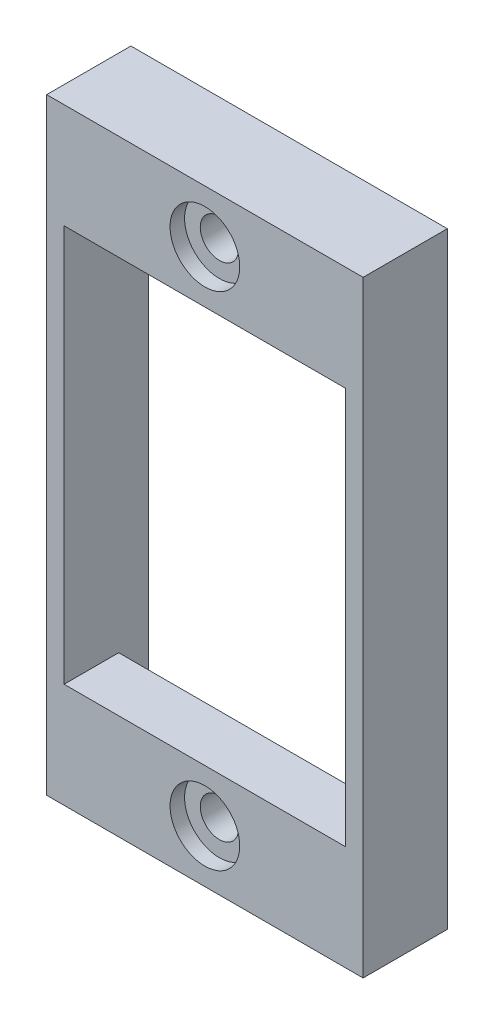
SolidWorks part; units mm, degrees
ref_plane "Front" through (0, 0, 0) normal (0, 0, 1) x (1, 0, 0)
ref_plane "Top" through (0, 0, 0) normal (0, 1, 0) x (1, 0, 0)
ref_plane "Right" through (0, 0, 0) normal (1, 0, 0) x (0, 0, -1)
sketch "Sketch1" plane through (0, 0, 0) normal (0, 0, 1) x (1, 0, 0)
  line L0 (0, 24.5) -> (0, -24.5) construction
  line L1 (-12, -24.5) -> (12, -24.5) construction
  line L2 (-12, -24.5) -> (-12, 24.5) construction
  line L3 (-12, 24.5) -> (12, 24.5) construction
  line L4 (12, -24.5) -> (12, 24.5) construction
  line L5 (-12, 0) -> (12, 0) construction
  line L6 (-12.12, -24.62) -> (-12.12, 24.62)
  line L7 (-12.12, 24.62) -> (12.12, 24.62)
  line L8 (12.12, -24.62) -> (12.12, 24.62)
  line L9 (-12.12, -24.62) -> (12.12, -24.62)
  line L10 (-13.62, -26.12) -> (-13.62, 26.12)
  line L11 (-13.62, 26.12) -> (13.62, 26.12)
  line L12 (13.62, -26.12) -> (13.62, 26.12)
  line L13 (-13.62, -26.12) -> (13.62, -26.12)
  circle A0 centre (0, 21.59) radius 1.5 construction
  circle A1 centre (0, -21.59) radius 1.5 construction
  dimension "D3" = 3
  dimension "D4" = 2.91
  dimension "D1" = 49
  dimension "D2" = 24
  dimension "D5" = 43.18
  dimension "D6" = 0.12
  dimension "D7" = 1.5
extrude "Boss-Extrude1" add sketch "Sketch1" along normal blind 0.25 and the other way blind 1.7
sketch "Sketch2" plane through (0, 0, 0.25) normal (0, 0, 1) x (1, 0, 0)
  line L0 (-12.12, 17.09) -> (12.12, 17.09)
  line L1 (-12.12, 24.62) -> (-12.12, -24.62) construction
  line L2 (12.12, -24.62) -> (12.12, 24.62) construction
  line L4 (13.62, -26.12) -> (13.62, 26.12) construction
  line L5 (13.62, -26.12) -> (13.62, 26.12)
  line L6 (-13.62, 26.12) -> (13.62, 26.12) construction
  line L7 (-13.62, 26.12) -> (13.62, 26.12)
  line L8 (-13.62, -26.12) -> (-13.62, 26.12) construction
  line L9 (-13.62, -26.12) -> (-13.62, 26.12)
  line L10 (-13.62, -26.12) -> (13.62, -26.12) construction
  line L11 (-13.62, -26.12) -> (13.62, -26.12)
  line L12 (-12, 0) -> (12, 0) construction
  line L13 (-12, 0) -> (12, 0) construction
  line L14 (-12.12, -17.09) -> (12.12, -17.09)
  line L15 (-12.12, 17.09) -> (-12.12, -17.09)
  line L16 (12.12, 17.09) -> (12.12, -17.09)
  circle A0 centre (0, 21.59) radius 1.5 construction
  dimension "D1" = 3
extrude "Boss-Extrude2" add sketch "Sketch2" along normal blind 1
sketch "Sketch3" plane through (0, 0, 1.25) normal (0, 0, 1) x (1, 0, 0)
  line L0 (12.12, 17.09) -> (-12.12, 17.09) construction
  line L1 (-4.62, 17.09) -> (-7.62, 17.09)
  line L2 (-12.12, -17.09) -> (12.12, -17.09) construction
  line L3 (-7.62, -17.09) -> (-4.62, -17.09)
  line L4 (-7.62, 17.09) -> (-7.62, -17.09)
  line L5 (-13.62, -26.12) -> (-13.62, 26.12) construction
  line L6 (-4.62, 17.09) -> (-4.62, -17.09)
  dimension "D1" = 6
  dimension "D2" = 3
extrude "Boss-Extrude3" add sketch "Sketch3" against normal up to surface (1 mm away) up to face at (0, 20.855, 0.25)
sketch "Sketch4" plane through (0, 0, 1.25) normal (0, 0, 1) x (1, 0, 0)
  line L0 (-13.62, 26.12) -> (-13.62, -26.12) construction
  line L1 (-7.62, -17.09) -> (-13.62, -17.09)
  line L2 (-7.62, -17.09) -> (-7.62, 17.09)
  line L3 (-7.62, 17.09) -> (-13.62, 17.09)
  line L4 (-13.62, -17.09) -> (-13.62, 17.09)
  line L5 (-7.62, 17.09) -> (-12.12, 17.09) construction
extrude "Cut-Extrude1" cut sketch "Sketch4" against normal up to surface (2.95 mm away) up to face at (0, 0, -1.7)
sketch "Sketch5" plane through (0, 24.62, 0) normal (0, -1, 0) x (1, 0, 0)
  line L0 (0, 0.25) -> (0, -1.7) construction
  line L1 (12.12, 0.25) -> (-12.12, 0.25) construction
  line L2 (12.12, -1.7) -> (-12.12, -1.7) construction
  line L4 (1.5, -1.5) -> (-1.5, -1.5)
  line L5 (1.5, -1.5) -> (1.5, -1.7)
  line L6 (1.5, -1.7) -> (-1.5, -1.7)
  line L7 (-1.5, -1.5) -> (-1.5, -1.7)
  line L8 (1.5, -1.5) -> (-1.5, -1.7) construction
  line L9 (1.5, -1.7) -> (-1.5, -1.5) construction
  point P6 (0, -1.6)
  dimension "D1" = 1.75
  dimension "D2" = 3
extrude "Boss-Extrude4" add sketch "Sketch5" along normal blind 0.5
mirror "Mirror1" about plane through (0, 0, 0) normal (0, 1, 0) of "Boss-Extrude4"
sketch "Sketch6" plane through (0, 0, -1.7) normal (0, 0, -1) x (-1, 0, 0)
  line L20 (13.62, -26.12) -> (13.62, -17.09)
  line L21 (13.62, -17.09) -> (12.12, -17.09)
  line L22 (12.12, -17.09) -> (12.12, -24.62)
  line L23 (12.12, -24.62) -> (1.5, -24.62)
  line L24 (1.5, -24.62) -> (1.5, -24.12)
  line L25 (1.5, -24.12) -> (-1.5, -24.12)
  line L26 (-1.5, -24.12) -> (-1.5, -24.62)
  line L27 (-1.5, -24.62) -> (-12.12, -24.62)
  line L28 (-12.12, -24.62) -> (-12.12, 24.62)
  line L29 (-12.12, 24.62) -> (-1.5, 24.62)
  line L30 (-1.5, 24.62) -> (-1.5, 24.12)
  line L31 (-1.5, 24.12) -> (1.5, 24.12)
  line L32 (1.5, 24.12) -> (1.5, 24.62)
  line L33 (1.5, 24.62) -> (12.12, 24.62)
  line L34 (12.12, 24.62) -> (12.12, 17.09)
  line L35 (12.12, 17.09) -> (13.62, 17.09)
  line L36 (13.62, 17.09) -> (13.62, 26.12)
  line L37 (13.62, 26.12) -> (-13.62, 26.12)
  line L38 (-13.62, 26.12) -> (-13.62, -26.12)
  line L39 (-13.62, -26.12) -> (13.62, -26.12)
  line L40 (13.62, -26.12) -> (13.62, -17.09)
  line L41 (13.62, -17.09) -> (12.12, -17.09)
  line L42 (12.12, -17.09) -> (12.12, -24.62)
  line L43 (12.12, -24.62) -> (1.5, -24.62)
  line L44 (1.5, -24.62) -> (1.5, -24.12)
  line L45 (1.5, -24.12) -> (-1.5, -24.12)
  line L46 (-1.5, -24.12) -> (-1.5, -24.62)
  line L47 (-1.5, -24.62) -> (-12.12, -24.62)
  line L48 (-12.12, -24.62) -> (-12.12, 24.62)
  line L49 (-12.12, 24.62) -> (-1.5, 24.62)
  line L50 (-1.5, 24.62) -> (-1.5, 24.12)
  line L51 (-1.5, 24.12) -> (1.5, 24.12)
  line L52 (1.5, 24.12) -> (1.5, 24.62)
  line L53 (1.5, 24.62) -> (12.12, 24.62)
  line L54 (12.12, 24.62) -> (12.12, 17.09)
  line L55 (12.12, 17.09) -> (13.62, 17.09)
  line L56 (13.62, 17.09) -> (13.62, 26.12)
  line L57 (13.62, 26.12) -> (-13.62, 26.12)
  line L58 (-13.62, 26.12) -> (-13.62, -26.12)
  line L59 (-13.62, -26.12) -> (13.62, -26.12)
  dimension "D1" = 0
extrude "Boss-Extrude5" add sketch "Sketch6" along normal blind 0.6
fillet "Fillet1" radius 1 4 edges at (1.5, -24.62, -1.9) (-1.5, -24.62, -1.9) (1.5, 24.62, -1.9) (-1.5, 24.62, -1.9)
sketch "Sketch8" plane through (0, 0, 1.25) normal (0, 0, 1) x (1, 0, 0)
  line L0 (-4.62, -17.09) -> (-4.62, 17.09) construction
  line L1 (-4.62, -17.09) -> (-4.62, 17.09)
  line L2 (12.12, 17.09) -> (-4.62, 17.09) construction
  line L3 (12.12, 17.09) -> (-4.62, 17.09)
  line L4 (-4.62, -17.09) -> (12.12, -17.09) construction
  line L5 (-4.62, -17.09) -> (12.12, -17.09)
  line L6 (12.12, -17.09) -> (12.12, 17.09) construction
  line L7 (12.12, -17.09) -> (12.12, 17.09)
  line L8 (-7.62, -17.09) -> (-13.62, -17.09)
  line L9 (-13.62, -17.09) -> (-13.62, -26.12)
  line L10 (-13.62, -26.12) -> (13.62, -26.12)
  line L11 (13.62, -26.12) -> (13.62, 26.12)
  line L12 (13.62, 26.12) -> (-13.62, 26.12)
  line L13 (-13.62, 26.12) -> (-13.62, 17.09)
  line L14 (-13.62, 17.09) -> (-7.62, 17.09)
  line L15 (-7.62, 17.09) -> (-7.62, -17.09)
  line L16 (-7.62, -17.09) -> (-13.62, -17.09)
  line L17 (-13.62, -17.09) -> (-13.62, -26.12)
  line L18 (-13.62, -26.12) -> (13.62, -26.12)
  line L19 (13.62, -26.12) -> (13.62, 26.12)
  line L20 (13.62, 26.12) -> (-13.62, 26.12)
  line L21 (-13.62, 26.12) -> (-13.62, 17.09)
  line L22 (-13.62, 17.09) -> (-7.62, 17.09)
  line L23 (-7.62, 17.09) -> (-7.62, -17.09)
  dimension "D1" = 0
extrude "Boss-Extrude6" add sketch "Sketch8" along normal blind 3.7
sketch "Sketch7" plane through (0, 0, 0.25) normal (0, 0, -1) x (-1, 0, 0)
  circle A2 centre (0, 21.59) radius 1.65
  circle A3 centre (0, -21.59) radius 1.65
  dimension "D1" = 3.3
extrude "Cut-Extrude2" cut sketch "Sketch7" against normal up to surface (4.7 mm away) up to face at (-5.31, 0, 4.95)
sketch "Sketch10" plane through (0, 0, 4.95) normal (0, 0, 1) x (1, 0, 0)
  line L0 (13.62, 0) -> (-7.62, 0) construction
  line L1 (13.62, -26.12) -> (13.62, 26.12) construction
  line L2 (-7.62, 17.09) -> (-7.62, -17.09) construction
  circle A0 centre (0, 21.59) radius 3
  circle A1 centre (0, -21.59) radius 3
  dimension "D1" = 6
extrude "Cut-Extrude3" cut sketch "Sketch10" against normal blind 1.25
sketch "Sketch11" plane through (0, 0, 0.25) normal (0, 0, -1) x (-1, 0, 0)
  line L0 (4.62, 0) -> (-12.12, 0) construction
  line L1 (4.62, 17.09) -> (4.62, -17.09) construction
  line L2 (-12.12, -24.62) -> (-12.12, -17.09) construction
  line L8 (-12.12, 0.995) -> (8.88, 0.995) construction
  line L9 (-12.12, 0.995) -> (-12.12, 16.095) construction
  line L10 (-12.12, 16.095) -> (8.88, 16.095) construction
  line L11 (8.88, 0.995) -> (8.88, 16.095) construction
  line L12 (8.88, 8.545) -> (-12.12, 8.545) construction
  line L13 (-12.12, -17.09) -> (-12.12, 17.09) construction
  line L14 (-1.62, 0.995) -> (-1.62, 16.095) construction
  line L15 (-4.87, 5.895) -> (1.63, 5.895) construction
  line L16 (-4.87, 5.895) -> (-4.87, 12.395) construction
  line L17 (-4.87, 12.395) -> (1.63, 12.395) construction
  line L18 (1.63, 5.895) -> (1.63, 12.395) construction
  line L19 (-4.87, 5.895) -> (1.63, 12.395) construction
  line L20 (-4.87, 12.395) -> (1.63, 5.895) construction
  line L21 (-4.87, -12.395) -> (1.63, -5.895) construction
  line L22 (-4.87, -5.895) -> (1.63, -12.395) construction
  line L23 (1.63, -5.895) -> (1.63, -12.395) construction
  line L24 (-4.87, -12.395) -> (1.63, -12.395) construction
  line L25 (-4.87, -5.895) -> (-4.87, -12.395) construction
  line L26 (-4.87, -5.895) -> (1.63, -5.895) construction
  line L27 (-1.62, -0.995) -> (-1.62, -16.095) construction
  line L28 (8.88, -8.545) -> (-12.12, -8.545) construction
  line L29 (8.88, -0.995) -> (8.88, -16.095) construction
  line L30 (-12.12, -16.095) -> (8.88, -16.095) construction
  line L31 (-12.12, -0.995) -> (-12.12, -16.095) construction
  line L32 (-12.12, -0.995) -> (8.88, -0.995) construction
  line L33 (-0.12, -1.995) -> (-0.12, -0.995) construction
  line L34 (-3.12, 1.995) -> (-0.12, 1.995) construction
  line L35 (-3.12, 1.995) -> (-3.12, 0.995) construction
  line L36 (-3.12, 0.995) -> (-0.12, 0.995) construction
  line L37 (-0.12, 1.995) -> (-0.12, 0.995) construction
  line L38 (-3.12, 1.995) -> (-0.12, 0.995) construction
  line L39 (-3.12, 0.995) -> (-0.12, 1.995) construction
  line L40 (-3.12, -0.995) -> (-0.12, -1.995) construction
  line L41 (-3.12, -1.995) -> (-0.12, -0.995) construction
  line L42 (-3.12, -1.995) -> (-0.12, -1.995) construction
  line L43 (-3.12, -1.995) -> (-3.12, -0.995) construction
  line L44 (4.62, 0) -> (4.62, 17.09) construction
  circle A0 centre (-1.62, 9.145) radius 1.5 construction
  circle A2 centre (-9.21, 8.545) radius 1.5 construction
  circle A3 centre (5.97, 8.545) radius 1.5 construction
  circle A4 centre (5.97, -8.545) radius 1.5 construction
  circle A5 centre (-9.21, -8.545) radius 1.5 construction
  circle A6 centre (-1.62, -9.145) radius 1.5 construction
  point P8 (-1.62, 8.545)
  point P13 (4.62, 8.545)
  point P15 (-1.62, 9.145)
  point P49 (-1.62, -9.145)
  point P50 (-1.62, -8.545)
  point P51 (-1.62, 1.495)
  dimension "D5" = 3
  dimension "D6" = 3
  dimension "D7" = 1.41
  dimension "D8" = 1
  dimension "D1" = 21
  dimension "D2" = 15.1
  dimension "D3" = 6.5
  dimension "D4" = 0.6
  dimension "D9" = 3
sketch "Sketch12" plane through (0, 0, 0.25) normal (0, 0, -1) x (-1, 0, 0)
  line L0 (-4.87, 5.895) -> (-4.87, 12.395) construction
  line L1 (-12.12, -17.09) -> (-5.87, -17.09)
  line L2 (-12.12, -17.09) -> (-12.12, 17.09)
  line L3 (-12.12, 17.09) -> (-5.87, 17.09)
  line L4 (-5.87, -17.09) -> (-5.87, 17.09)
  line L6 (7.62, 17.09) -> (12.12, 17.09) construction
  line L7 (2.63, -17.09) -> (9.87, -17.09)
  line L8 (2.63, -17.09) -> (2.63, 17.09)
  line L9 (2.63, 17.09) -> (9.87, 17.09)
  line L10 (9.87, -17.09) -> (9.87, 17.09)
  line L11 (1.63, 5.895) -> (1.63, 12.395) construction
  line L13 (-12.12, 17.09) -> (4.62, 17.09) construction
  line L14 (4.62, -17.09) -> (-12.12, -17.09) construction
  dimension "D1" = 1
  dimension "D2" = 1
extrude "Boss-Extrude7" add sketch "Sketch12" against normal up to surface (4.7 mm away) up to face at (3, 21.59, 4.95)
sketch "Sketch18" plane through (0, 0, 0.25) normal (0, 0, -1) x (-1, 0, 0)
  line L0 (2.63, -17.09) -> (9.87, -17.09)
  line L1 (9.87, -17.09) -> (9.87, 17.09)
  line L2 (9.87, 17.09) -> (2.63, 17.09)
  line L3 (2.63, 17.09) -> (2.63, -17.09)
extrude "Cut-Extrude6" cut sketch "Sketch18" against normal up to surface (4.7 mm away) up to face at (-5.8725, 0, 4.95)
sketch "Sketch19" plane through (0, -17.09, 0) normal (0, 1, 0) x (1, 0, 0)
  line L0 (-13.62, 2.3) -> (-13.62, -4.95) construction
  line L1 (-13.62, 2.3) -> (-13.62, -4.95)
  line L2 (-13.62, 2.3) -> (-12.12, 2.3) construction
  line L3 (-13.62, 2.3) -> (-12.12, 2.3)
  line L4 (-12.12, 2.3) -> (-12.12, -4.95)
  line L5 (-13.62, -4.95) -> (5.87, -4.95) construction
  line L6 (-12.12, -4.95) -> (-13.62, -4.95)
extrude "Boss-Extrude8" add sketch "Sketch19" along normal up to surface (34.18 mm away) up to face at (-6.6233, 17.09, 0.9667)
sketch "Sketch20" plane through (0, 0, 0.25) normal (0, 0, -1) x (-1, 0, 0)
  line L0 (-5.87, -17.09) -> (-5.87, 17.09) construction
  line L1 (-5.87, -17.09) -> (-5.87, 17.09)
  line L2 (-5.87, -17.09) -> (-12.12, -17.09)
  line L3 (-12.12, -24.62) -> (-12.12, 24.62) construction
  line L4 (-12.12, -17.09) -> (-12.12, 17.09)
  line L5 (-12.12, 17.09) -> (-5.87, 17.09)
extrude "Cut-Extrude7" cut sketch "Sketch20" against normal up to surface (4.7 mm away) up to face at (-3.125, 0, 4.95)
